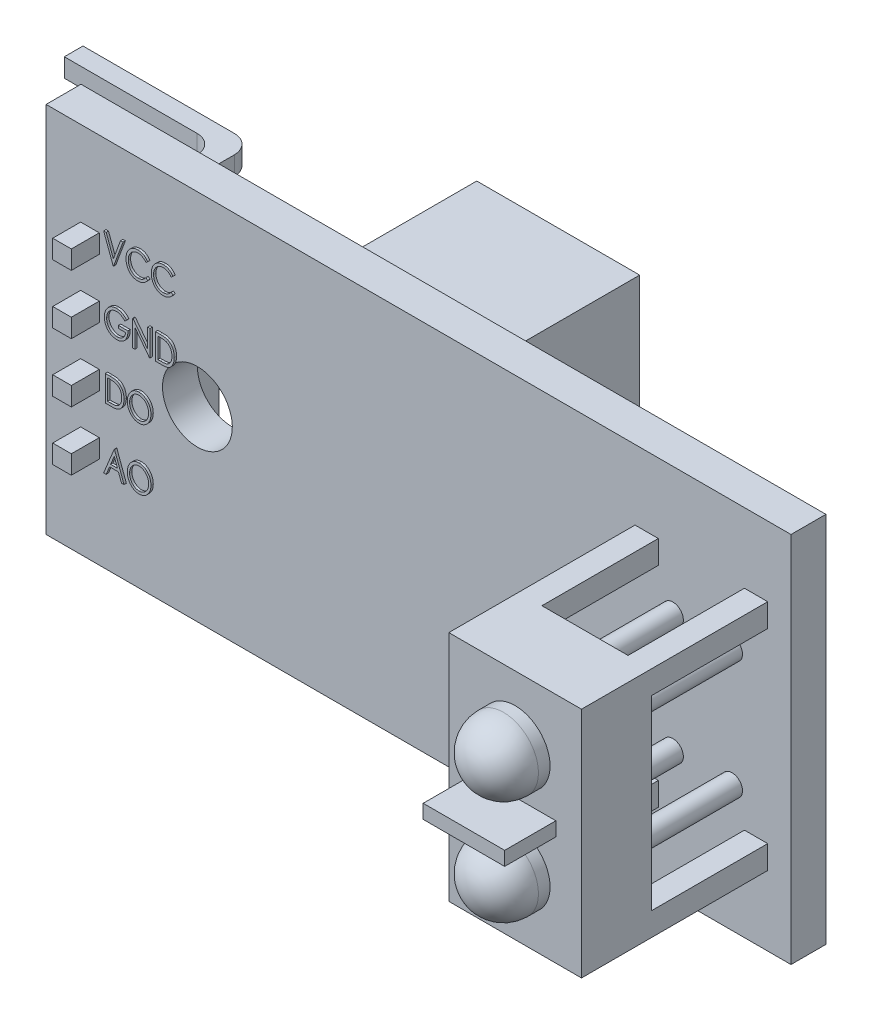
SolidWorks part; units mm, degrees
ref_plane "Спереди" through (0, 0, 0) normal (0, 0, 1) x (1, 0, 0)
ref_plane "Сверху" through (0, 0, 0) normal (0, 1, 0) x (1, 0, 0)
ref_plane "Справа" through (0, 0, 0) normal (1, 0, 0) x (0, 0, -1)
sketch "Эскиз1" plane through (0, 0, 0) normal (0, 0, 1) x (1, 0, 0)
  line L1 (0, 0) -> (32, 0)
  line L2 (0, 0) -> (0, -16)
  line L3 (0, -16) -> (32, -16)
  line L4 (32, 0) -> (32, -16)
  circle A0 centre (6.5, -8) radius 1.5
  point P7 (0, -8)
  dimension "D3" = 3
  dimension "D1" = 32
  dimension "D2" = 16
  dimension "D4" = 6.5
extrude "Бобышка-Вытянуть1" add sketch "Эскиз1" along normal blind 1.5
sketch "Эскиз2" plane through (0, 0, 1.5) normal (0, 0, 1) x (1, 0, 0)
  line L0 (32, -16) -> (32, 0) construction
  line L1 (25.3, -3) -> (31, -3)
  line L2 (25.3, -3) -> (25.3, -13)
  line L3 (25.3, -13) -> (31, -13)
  line L4 (31, -3) -> (31, -13)
  point P4 (32, -8)
  point P5 (31, -8)
  dimension "D1" = 10
  dimension "D2" = 5.7
  dimension "D3" = 1
extrude "Бобышка-Вытянуть2" add sketch "Эскиз2" along normal blind 8
sketch "Эскиз3" plane through (0, 0, 9.5) normal (0, 0, 1) x (1, 0, 0)
  line L0 (31, -3) -> (25.3, -3) construction
  line L1 (26.4, -7.7) -> (29.9, -7.7)
  line L2 (26.4, -7.7) -> (26.4, -8.3)
  line L3 (26.4, -8.3) -> (29.9, -8.3)
  line L4 (29.9, -7.7) -> (29.9, -8.3)
  line L5 (25.3, -3) -> (25.3, -13) construction
  point P4 (28.15, -3)
  point P5 (25.3, -8)
  point P8 (26.4, -8)
  point P11 (28.15, -7.7)
  dimension "D1" = 0.6
  dimension "D2" = 3.5
extrude "Бобышка-Вытянуть3" add sketch "Эскиз3" along normal blind 2.2
sketch "Эскиз4" plane through (0, 0, 9.5) normal (0, 0, 1) x (1, 0, 0)
  line L0 (28.15, -13) -> (28.15, -0.4007) construction
  line L1 (25.3, -13) -> (31, -13) construction
  circle A0 centre (28.15, -5.7911) radius 1.5
  circle A1 centre (28.15, -10.2911) radius 1.5
  dimension "D2" = 3
  dimension "D1" = 4.5
extrude "Бобышка-Вытянуть4" add sketch "Эскиз4" along normal blind 2
fillet "Скругление1" radius 1.5 2 edges at (29.65, -5.7911, 11.5) (29.65, -10.2911, 11.5)
sketch "Эскиз5" plane through (0, -13, 0) normal (0, -1, 0) x (1, 0, 0)
  line L0 (25.3, 1.5) -> (31, 1.5) construction
  line L1 (26.3, 1.5) -> (30, 1.5)
  line L2 (26.3, 1.5) -> (26.3, 6.5)
  line L3 (26.3, 6.5) -> (30, 6.5)
  line L4 (30, 1.5) -> (30, 6.5)
  line L5 (25.3, 9.5) -> (25.3, 1.5) construction
  line L6 (31, 9.5) -> (31, 1.5) construction
  dimension "D1" = 5
  dimension "D2" = 1
  dimension "D3" = 1
extrude "Вырез-Вытянуть1" cut sketch "Эскиз5" against normal through all
sketch "Эскиз7" plane through (31, 0, 0) normal (1, 0, 0) x (0, 0, -1)
  line L0 (-1.5, -13) -> (-1.5, -3) construction
  line L1 (-1.5, -12) -> (-6.5, -12)
  line L2 (-1.5, -12) -> (-1.5, -4)
  line L3 (-1.5, -4) -> (-6.5, -4)
  line L4 (-6.5, -12) -> (-6.5, -4)
  line L5 (-9.5, -13) -> (-1.5, -13) construction
  line L6 (-9.5, -3) -> (-1.5, -3) construction
  dimension "D1" = 5
  dimension "D2" = 1
  dimension "D3" = 1
extrude "Вырез-Вытянуть2" cut sketch "Эскиз7" against normal through all
sketch "Эскиз8" plane through (0, 0, 0) normal (0, 0, -1) x (-1, 0, 0)
  line L1 (-19, 0) -> (-12, 0)
  line L2 (-19, 0) -> (-19, -7)
  line L3 (-19, -7) -> (-12, -7)
  line L4 (-12, 0) -> (-12, -7)
  line L5 (-32, 0) -> (0, 0) construction
  line L6 (0, 0) -> (0, -16) construction
  dimension "D1" = 7
  dimension "D2" = 12
extrude "Бобышка-Вытянуть5" add sketch "Эскиз8" along normal blind 5
sketch "Эскиз9" plane through (0, 0, -5) normal (0, 0, -1) x (-1, 0, 0)
  circle A0 centre (-15.5, -3.5) radius 1.6
  dimension "D1" = 3.2
extrude "Вырез-Вытянуть3" cut sketch "Эскиз9" against normal blind 0.1
sketch "Эскиз10" plane through (0, 0, -4.9) normal (0, 0, -1) x (-1, 0, 0)
  line L0 (-17.0876, -3.3015) -> (-17.0876, -3.6985)
  line L1 (-17.0876, -3.6985) -> (-15.6862, -3.6985)
  line L2 (-15.6862, -5.0891) -> (-15.3015, -5.0891)
  line L3 (-15.6862, -1.9124) -> (-15.6862, -3.3015)
  line L4 (-17.0876, -3.3015) -> (-15.6862, -3.3015)
  line L5 (-15.3015, -1.9124) -> (-15.3015, -3.3015)
  line L6 (-15.6862, -3.6985) -> (-15.6862, -5.0891)
  line L7 (-15.3015, -5.0891) -> (-15.2991, -5.0873)
  line L8 (-15.3015, -3.3015) -> (-13.9124, -3.3015)
  line L9 (-13.9124, -3.6985) -> (-13.9124, -3.3015)
  line L10 (-15.3015, -1.9124) -> (-15.6862, -1.9124)
  line L11 (-15.3015, -3.6985) -> (-15.3015, -5.0891)
  line L14 (-15.3015, -3.6985) -> (-13.9124, -3.6985)
  circle A2 centre (-15.5, -3.5) radius 1.6 construction
  circle A3 centre (-15.5, -3.5) radius 1.6 construction
  circle M1 centre (-15.5, -3.5) radius 1.6
extrude "Вырез-Вытянуть4" cut sketch "Эскиз10" against normal blind 1 contours L11 L14 L9 L8 L5 L10 L3 L4 L0 L1 L6 L2 M1 region at (15.4972, -3.5004, -4.9)
sketch "Эскиз11" plane through (0, 0, 0) normal (0, 0, -1) x (-1, 0, 0)
  line L0 (0, 0) -> (0, -16) construction
  line L1 (-3.135, -3) -> (-0.635, -3)
  line L2 (-3.135, -3) -> (-3.135, -13)
  line L3 (-3.135, -13) -> (-0.635, -13)
  line L4 (-0.635, -3) -> (-0.635, -13)
  point P4 (-0.635, -8)
  point P5 (0, -8)
  dimension "D1" = 10
  dimension "D2" = 2.5
extrude "Бобышка-Вытянуть6" add sketch "Эскиз11" along normal blind 2.8
sketch "Эскиз12" plane through (0, 0, -2.8) normal (0, 0, -1) x (-1, 0, 0)
  line L0 (-1.885, -3) -> (-1.885, -6.4924) construction
  line L1 (-2.285, -3.635) -> (-1.485, -3.635)
  line L2 (-2.285, -3.635) -> (-2.285, -4.435)
  line L3 (-2.285, -4.435) -> (-1.485, -4.435)
  line L4 (-1.485, -3.635) -> (-1.485, -4.435)
  line L5 (-0.635, -3) -> (-3.135, -3) construction
  line L6 (-2.285, -6.175) -> (-1.485, -6.175)
  line L7 (-2.285, -6.175) -> (-2.285, -6.975)
  line L8 (-2.285, -6.975) -> (-1.485, -6.975)
  line L9 (-1.485, -6.175) -> (-1.485, -6.975)
  line L10 (-2.285, -8.715) -> (-1.485, -8.715)
  line L11 (-2.285, -8.715) -> (-2.285, -9.515)
  line L12 (-2.285, -9.515) -> (-1.485, -9.515)
  line L13 (-1.485, -8.715) -> (-1.485, -9.515)
  line L14 (-2.285, -11.255) -> (-1.485, -11.255)
  line L15 (-2.285, -11.255) -> (-2.285, -12.055)
  line L16 (-2.285, -12.055) -> (-1.485, -12.055)
  line L17 (-1.485, -11.255) -> (-1.485, -12.055)
  point P8 (-1.885, -3.635)
  point P15 (-1.885, -6.175)
  point P20 (-1.885, -8.715)
  point P25 (-1.885, -11.255)
  dimension "D1" = 0.8
  dimension "D2" = 0.635
  dimension "D3" = 4
extrude "Бобышка-Вытянуть7" add sketch "Эскиз12" along normal blind 2.3
sketch "Эскиз13" plane through (1.485, 0, 0) normal (-1, 0, 0) x (0, 0, 1)
  line L0 (-5.1, -4.435) -> (-2.8, -4.435) construction
  line L1 (-5.1, -3.635) -> (-4.3, -3.635)
  line L2 (-5.1, -3.635) -> (-5.1, -4.435)
  line L3 (-5.1, -4.435) -> (-4.3, -4.435)
  line L4 (-4.3, -3.635) -> (-4.3, -4.435)
  line L5 (-5.1, -6.175) -> (-4.3, -6.175)
  line L6 (-5.1, -6.175) -> (-5.1, -6.975)
  line L7 (-5.1, -6.975) -> (-4.3, -6.975)
  line L8 (-4.3, -6.175) -> (-4.3, -6.975)
  line L9 (-5.1, -8.715) -> (-4.3, -8.715)
  line L10 (-5.1, -8.715) -> (-5.1, -9.515)
  line L11 (-5.1, -9.515) -> (-4.3, -9.515)
  line L12 (-4.3, -8.715) -> (-4.3, -9.515)
  line L13 (-5.1, -11.255) -> (-4.3, -11.255)
  line L14 (-5.1, -11.255) -> (-5.1, -12.055)
  line L15 (-5.1, -12.055) -> (-4.3, -12.055)
  line L16 (-4.3, -11.255) -> (-4.3, -12.055)
  dimension "D1" = 4
extrude "Бобышка-Вытянуть8" add sketch "Эскиз13" along normal blind 6.5
fillet "Скругление2" radius 0.8 8 edges at (1.485, -4.035, -4.3) (1.485, -6.575, -4.3) (1.485, -9.115, -4.3) (1.485, -11.655, -4.3) (2.285, -11.655, -5.1) (2.285, -9.115, -5.1) (2.285, -6.575, -5.1) (2.285, -4.035, -5.1)
sketch "Эскиз14" plane through (0, 0, 1.5) normal (0, 0, 1) x (1, 0, 0)
  line L0 (1.485, -11.255) -> (2.285, -11.255) construction
  line L1 (1.485, -12.055) -> (2.285, -12.055)
  line L2 (1.485, -12.055) -> (1.485, -11.255)
  line L3 (1.485, -11.255) -> (2.285, -11.255)
  line L4 (2.285, -12.055) -> (2.285, -11.255)
  line L5 (2.285, -11.255) -> (2.285, -12.055) construction
  line L6 (1.485, -9.515) -> (2.285, -9.515)
  line L7 (1.485, -9.515) -> (1.485, -8.715)
  line L8 (1.485, -8.715) -> (2.285, -8.715)
  line L9 (2.285, -9.515) -> (2.285, -8.715)
  line L10 (1.485, -6.975) -> (2.285, -6.975)
  line L11 (1.485, -6.975) -> (1.485, -6.175)
  line L12 (1.485, -6.175) -> (2.285, -6.175)
  line L13 (2.285, -6.975) -> (2.285, -6.175)
  line L14 (1.485, -4.435) -> (2.285, -4.435)
  line L15 (1.485, -4.435) -> (1.485, -3.635)
  line L16 (1.485, -3.635) -> (2.285, -3.635)
  line L17 (2.285, -4.435) -> (2.285, -3.635)
  dimension "D1" = 0.8
  dimension "D2" = 4
extrude "Бобышка-Вытянуть9" add sketch "Эскиз14" along normal blind 1.2
sketch "Эскиз15" plane through (0, 0, 1.5) normal (0, 0, 1) x (1, 0, 0)
  text T0 "VCC\r\nGND\r\nDO\r\nAO" font "Century Gothic" height 1.1
extrude "Бобышка-Вытянуть10" add sketch "Эскиз15" along normal blind 0.1
sketch "Эскиз16" plane through (0, 0, 0) normal (0, 1, 0) x (1, 0, 0)
  line L1 (19, 5) -> (12, 5)
  line L2 (19, 5) -> (19, 0)
  line L3 (19, 0) -> (12, 0)
  line L4 (12, 5) -> (12, 0)
extrude "Вырез-Вытянуть5" cut sketch "Эскиз16" against normal blind 0.1
sketch "Эскиз17" plane through (0, 0, 0) normal (0, 0, -1) x (-1, 0, 0)
  circle A0 centre (-29.4665, -5.4995) radius 0.45
  circle A1 centre (-26.9265, -5.4995) radius 0.45
  circle A2 centre (-29.4665, -10.5795) radius 0.45
  circle A3 centre (-26.9265, -10.5795) radius 0.45
  dimension "D1" = 0.9
  dimension "D2" = 2
  dimension "D3" = 2
extrude "Бобышка-Вытянуть11" add sketch "Эскиз17" along normal blind 0.9 and the other way blind 8
sketch "Эскиз18" plane through (0, 0, 0) normal (0, 0, -1) x (-1, 0, 0)
  line L1 (-17.421, -8.8059) -> (-12.921, -8.8059)
  line L2 (-17.421, -8.8059) -> (-17.421, -14.3059)
  line L3 (-17.421, -14.3059) -> (-12.921, -14.3059)
  line L4 (-12.921, -8.8059) -> (-12.921, -14.3059)
  dimension "D1" = 4.5
  dimension "D2" = 5.5
extrude "Бобышка-Вытянуть12" add sketch "Эскиз18" along normal blind 1.6
sketch "Эскиз19" plane through (0, 0, 0) normal (0, 0, -1) x (-1, 0, 0)
  line L0 (-17.421, -8.8059) -> (-17.421, -14.3059) construction
  line L1 (-19.421, -9.1779) -> (-17.421, -9.1779)
  line L2 (-19.421, -9.1779) -> (-19.421, -9.6779)
  line L3 (-19.421, -9.6779) -> (-17.421, -9.6779)
  line L4 (-17.421, -9.1779) -> (-17.421, -9.6779)
  line L5 (-15.171, -8.8059) -> (-15.171, -17.6918) construction
  line L6 (-12.921, -8.8059) -> (-17.421, -8.8059) construction
  line L7 (-19.421, -10.5843) -> (-17.421, -10.5843)
  line L8 (-19.421, -10.5843) -> (-19.421, -11.0843)
  line L9 (-19.421, -11.0843) -> (-17.421, -11.0843)
  line L10 (-17.421, -10.5843) -> (-17.421, -11.0843)
  line L11 (-19.421, -11.9907) -> (-17.421, -11.9907)
  line L12 (-19.421, -11.9907) -> (-19.421, -12.4907)
  line L13 (-19.421, -12.4907) -> (-17.421, -12.4907)
  line L14 (-17.421, -11.9907) -> (-17.421, -12.4907)
  line L15 (-19.421, -13.3972) -> (-17.421, -13.3972)
  line L16 (-19.421, -13.3972) -> (-19.421, -13.8972)
  line L17 (-19.421, -13.8972) -> (-17.421, -13.8972)
  line L18 (-17.421, -13.3972) -> (-17.421, -13.8972)
  line L19 (-12.921, -13.3972) -> (-12.921, -13.8972)
  line L20 (-10.921, -13.8972) -> (-12.921, -13.8972)
  line L21 (-10.921, -13.3972) -> (-10.921, -13.8972)
  line L22 (-10.921, -13.3972) -> (-12.921, -13.3972)
  line L23 (-12.921, -11.9907) -> (-12.921, -12.4907)
  line L24 (-10.921, -12.4907) -> (-12.921, -12.4907)
  line L25 (-10.921, -11.9907) -> (-10.921, -12.4907)
  line L26 (-10.921, -11.9907) -> (-12.921, -11.9907)
  line L27 (-12.921, -10.5843) -> (-12.921, -11.0843)
  line L28 (-10.921, -11.0843) -> (-12.921, -11.0843)
  line L29 (-10.921, -10.5843) -> (-10.921, -11.0843)
  line L30 (-10.921, -10.5843) -> (-12.921, -10.5843)
  line L31 (-12.921, -9.1779) -> (-12.921, -9.6779)
  line L32 (-10.921, -9.6779) -> (-12.921, -9.6779)
  line L33 (-10.921, -9.1779) -> (-10.921, -9.6779)
  line L34 (-10.921, -9.1779) -> (-12.921, -9.1779)
  dimension "D1" = 0.5
  dimension "D2" = 2
  dimension "D3" = 4
extrude "Бобышка-Вытянуть13" add sketch "Эскиз19" along normal blind 1
chamfer "Фаска1" distance 0.5 angle 50 8 edges at (10.921, -9.4279, -1) (10.921, -10.8343, -1) (10.921, -12.2407, -1) (10.921, -13.6472, -1) (19.421, -9.4279, -1) (19.421, -10.8343, -1) (19.421, -12.2407, -1) (19.421, -13.6472, -1) first distance on face at (10.921, -9.4279, -0.5) first distance on face at (10.921, -10.8343, -0.5) first distance on face at (10.921, -12.2407, -0.5) first distance on face at (10.921, -13.6472, -0.5) first distance on face at (19.421, -9.4279, -0.5) first distance on face at (19.421, -10.8343, -0.5) first distance on face at (19.421, -12.2407, -0.5) first distance on face at (19.421, -13.6472, -0.5)
sketch "Эскиз21" plane through (0, -13.8972, 0) normal (0, -1, 0) x (1, 0, 0)
  line L1 (17.421, 0) -> (18.421, 0)
  line L2 (17.421, 0) -> (17.421, -0.5)
  line L3 (17.421, -0.5) -> (18.421, -0.5)
  line L4 (18.421, 0) -> (18.421, -0.5)
  dimension "D1" = 0.5
  dimension "D2" = 1
extrude "Вырез-Вытянуть6" cut sketch "Эскиз21" against normal blind 5
sketch "Эскиз22" plane through (0, -13.8972, 0) normal (0, -1, 0) x (1, 0, 0)
  line L1 (12.921, 0) -> (11.921, 0)
  line L2 (12.921, 0) -> (12.921, -0.5)
  line L3 (12.921, -0.5) -> (11.921, -0.5)
  line L4 (11.921, 0) -> (11.921, -0.5)
  dimension "D1" = 0.5
  dimension "D2" = 1
extrude "Вырез-Вытянуть7" cut sketch "Эскиз22" against normal blind 5
chamfer "Фаска2" distance 0.5 angle 50 1 edges at (12.921, -11.5559, -1.6) first distance on face at (12.921, -12.2407, -0.75)
sketch "Эскиз23" plane through (0, 0, -1.6) normal (0, 0, -1) x (-1, 0, 0)
  line L0 (-14.7983, -14.3059) -> (-14.7983, -9.7396) construction
  line L1 (-17.421, -14.3059) -> (-13.5168, -14.3059) construction
  text T0 "LM393" font "Century Gothic" height 1
extrude "Вырез-Вытянуть8" cut sketch "Эскиз23" against normal blind 0.1
